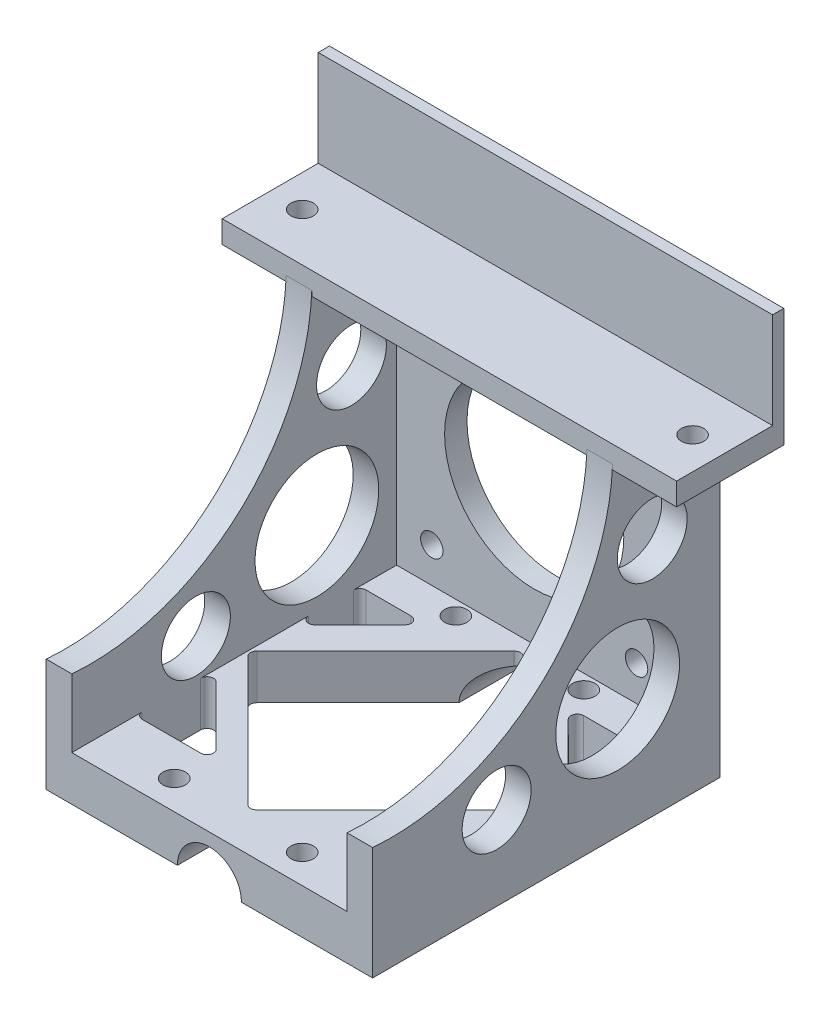
SolidWorks part; units mm, degrees
ref_plane "Front Plane" through (0, 0, 0) normal (0, 0, 1) x (1, 0, 0)
ref_plane "Top Plane" through (0, 0, 0) normal (0, 1, 0) x (1, 0, 0)
ref_plane "Right Plane" through (0, 0, 0) normal (1, 0, 0) x (0, 0, -1)
sketch "Sketch1" plane through (0, 0, 0) normal (0, 0, 1) x (1, 0, 0)
  line L1 (-51.9324, 28.7717) -> (-0.9324, 28.7717)
  line L2 (-51.9324, 28.7717) -> (-51.9324, -24.7283)
  line L3 (-51.9324, -24.7283) -> (-0.9324, -24.7283)
  line L4 (-0.9324, 28.7717) -> (-0.9324, -24.7283)
  dimension "D1" = 51
  dimension "D2" = 53.5
extrude "Boss-Extrude1" add sketch "Sketch1" along normal blind 54.25
sketch "Sketch2" plane through (0, 0, 54.25) normal (0, 0, 1) x (1, 0, 0)
  line L0 (-0.9324, -24.7283) -> (-0.9324, 28.7717) construction
  line L1 (-47.9324, -17.7283) -> (-4.9324, -17.7283)
  line L2 (-47.9324, -17.7283) -> (-47.9324, 25.2717)
  line L3 (-47.9324, 25.2717) -> (-4.9324, 25.2717)
  line L4 (-4.9324, -17.7283) -> (-4.9324, 25.2717)
  line L6 (-51.9324, -24.7283) -> (-0.9324, -24.7283) construction
  dimension "D1" = 43
  dimension "D2" = 43
  dimension "D3" = 4
  dimension "D4" = 7
extrude "Cut-Extrude1" cut sketch "Sketch2" against normal offset from surface (50.75 mm away) 3.5 up to face at (-26.4324, 2.0217, 0)
sketch "Sketch3" plane through (0, 0, 54.25) normal (0, 0, 1) x (1, 0, 0)
  line L0 (-0.9324, 28.7717) -> (-51.9324, 28.7717) construction
  line L1 (-47.9324, 25.2717) -> (-4.9324, 25.2717)
  line L2 (-47.9324, 25.2717) -> (-47.9324, 28.7717)
  line L3 (-47.9324, 28.7717) -> (-4.9324, 28.7717)
  line L4 (-4.9324, 25.2717) -> (-4.9324, 28.7717)
extrude "Cut-Extrude2" cut sketch "Sketch3" against normal offset from surface (37.5 mm away) 16.75 up to face at (-26.4324, 2.0217, 0)
sketch "Sketch4" plane through (-51.9324, 0, 0) normal (-1, 0, 0) x (0, 0, 1)
  line L0 (16.75, 25.2717) -> (16.75, 28.7717) construction
  line L1 (54.25, 28.7717) -> (54.25, -24.7283) construction
  line L3 (16.75, 28.7717) -> (54.25, 28.7717)
  line L4 (54.25, 28.7717) -> (54.25, -7.0747)
  arc A0 (16.75, 28.7717) -> (54.25, -7.0747) centre (51.3457, 27.4252) ccw
extrude "Cut-Extrude3" cut sketch "Sketch4" against normal blind 76
sketch "Sketch5" plane through (-51.9324, 0, 0) normal (-1, 0, 0) x (0, 0, 1)
  circle A0 centre (15.9549, -6.117) radius 9.6731
  circle A1 centre (34.8683, -11.6526) radius 5.3908
  circle A2 centre (10.5511, 12.8623) radius 5.4569
extrude "Cut-Extrude4" cut sketch "Sketch5" against normal blind 76
sketch "Sketch6" plane through (0, 0, 3.5) normal (0, 0, 1) x (1, 0, 0)
  line L0 (-4.9324, 25.2717) -> (-47.9324, -17.7283) construction
  line L1 (-4.9324, -17.7283) -> (-47.9324, 25.2717) construction
  circle A0 centre (-26.4324, 3.7717) radius 14
  circle A1 centre (-10.4324, 19.7717) radius 1.75
  circle A2 centre (-42.4324, 19.7717) radius 1.75
  circle A3 centre (-42.4324, -12.2283) radius 1.75
  circle A4 centre (-10.4324, -12.2283) radius 1.75
  dimension "D2" = 28
  dimension "D3" = 3.5
  dimension "D1" = 32
extrude "Cut-Extrude5" cut sketch "Sketch6" against normal blind 76
sketch "Sketch7" plane through (0, 0, 0) normal (0, 0, -1) x (-1, 0, 0)
  line L0 (51.9324, -24.7283) -> (0.9324, -24.7283) construction
  circle A0 centre (26.4324, -24.7283) radius 5
  dimension "D1" = 10
extrude "Cut-Extrude6" cut sketch "Sketch7" against normal blind 76
sketch "Sketch8" plane through (0, -24.7283, 0) normal (0, -1, 0) x (1, 0, 0)
  line L0 (-26.4324, 54.25) -> (-26.4324, 0) construction
  line L1 (-21.4324, 54.25) -> (-31.4324, 54.25) construction
  line L2 (-31.4324, 0) -> (-21.4324, 0) construction
  line L3 (-26.4324, 48.25) -> (-4.9324, 26.75)
  line L4 (-4.9324, 3.5) -> (-4.9324, 54.25) construction
  line L5 (-4.9324, 26.75) -> (-26.4324, 5.25)
  line L7 (-26.4324, 5.25) -> (-47.9324, 26.75)
  line L8 (-47.9324, 26.75) -> (-26.4324, 48.25)
  line L9 (-47.9324, 3.5) -> (-47.9324, 54.25) construction
  line L10 (-26.4324, 5.25) -> (-4.9324, 5.25) construction
  line L11 (-26.4324, 5.25) -> (-47.9324, 5.25) construction
  line L12 (-26.4324, 48.25) -> (-47.9324, 48.25) construction
  line L13 (-26.4324, 48.25) -> (-4.9324, 48.25) construction
  line L14 (-15.3613, 44.25) -> (-4.9324, 44.25)
  line L15 (-4.9324, 44.25) -> (-4.9324, 33.8211)
  line L16 (-4.9324, 33.8211) -> (-15.3613, 44.25)
  line L17 (-4.9324, 9.25) -> (-15.3613, 9.25)
  line L18 (-15.3613, 9.25) -> (-4.9324, 19.6789)
  line L19 (-4.9324, 19.6789) -> (-4.9324, 9.25)
  line L20 (-47.9324, 9.25) -> (-37.5034, 9.25)
  line L21 (-37.5034, 9.25) -> (-47.9324, 19.6789)
  line L22 (-47.9324, 19.6789) -> (-47.9324, 9.25)
  line L23 (-47.9324, 44.25) -> (-35.3821, 44.25)
  line L24 (-35.3821, 44.25) -> (-47.9324, 31.6997)
  line L25 (-47.9324, 31.6997) -> (-47.9324, 44.25)
  dimension "D1" = 6
  dimension "D2" = 45
  dimension "D3" = 4
  dimension "D4" = 45
  dimension "D5" = 5
  dimension "D6" = 4
  dimension "D7" = 5
  dimension "D8" = 5
extrude "Cut-Extrude7" cut sketch "Sketch8" against normal blind 27
fillet "Fillet2" radius 1 16 edges at (-47.9324, -21.2283, 31.6997) (-4.9324, -21.2283, 33.8211) (-4.9324, -21.2283, 19.6789) (-47.9324, -21.2283, 19.6789) (-15.3613, -21.2283, 9.25) (-37.5034, -21.2283, 9.25) (-26.4324, -18.7283, 5.25) (-4.9324, -21.2283, 9.25) (-47.9324, -21.2283, 9.25) (-47.9324, -21.2283, 26.75) (-4.9324, -21.2283, 26.75) (-4.9324, -21.2283, 44.25) (-47.9324, -21.2283, 44.25) (-35.3821, -21.2283, 44.25) (-15.3613, -21.2283, 44.25) (-26.4324, -18.7283, 48.25)
sketch "Sketch12" plane through (0, -24.7283, 0) normal (0, -1, 0) x (1, 0, 0)
  line L0 (-21.4324, 54.25) -> (-0.9324, 54.25) construction
  line L1 (-47.9324, 54.25) -> (-4.9324, 54.25) construction
  line L2 (-21.4324, 54.25) -> (-31.4324, 54.25) construction
  line L3 (-21.4324, 0) -> (-0.9324, 0) construction
  circle A0 centre (-16.4324, 49.75) radius 1.75
  circle A1 centre (-36.4324, 49.75) radius 1.75
  circle A2 centre (-16.4324, 5.75) radius 1.75
  circle A3 centre (-36.4324, 5.75) radius 1.75
  point P10 (-26.4324, 54.25)
  point P13 (-26.4324, 54.25)
  dimension "D1" = 4.5
  dimension "D2" = 10
  dimension "D3" = 10
  dimension "D4" = 5.75
extrude "Cut-Extrude8" cut sketch "Sketch12" against normal blind 15
sketch "Sketch13" plane through (-51.9324, 0, 0) normal (-1, 0, 0) x (0, 0, 1)
  line L0 (3.5, 25.2717) -> (16.75, 25.2717) construction
  line L1 (0, 28.7717) -> (16.75, 28.7717)
  line L2 (0, 28.7717) -> (0, 25.2717)
  line L3 (0, 25.2717) -> (16.75, 25.2717)
  line L4 (16.75, 28.7717) -> (16.75, 25.2717)
  line L5 (16.75, 28.7717) -> (0, 28.7717) construction
  arc A0 (16.75, 28.7717) -> (54.25, -7.0747) centre (51.3457, 27.4252) ccw construction
extrude "Boss-Extrude4" add sketch "Sketch13" along normal blind 10 and the other way offset from surface (61 mm away) 10 other way up to face at (-0.9324, 7.4054, 10.5511)
sketch "Sketch14" plane through (0, 28.7717, 0) normal (0, 1, 0) x (1, 0, 0)
  line L0 (9.0676, 0) -> (9.0676, -16.75) construction
  line L1 (-61.9324, 0) -> (9.0676, 0)
  line L2 (-61.9324, 0) -> (-61.9324, -1.75)
  line L3 (-61.9324, -1.75) -> (9.0676, -1.75)
  line L4 (9.0676, 0) -> (9.0676, -1.75)
  dimension "D1" = 1.75
extrude "Boss-Extrude5" add sketch "Sketch14" along normal blind 15
sketch "Sketch15" plane through (0, 25.2717, 0) normal (0, -1, 0) x (1, 0, 0)
  line L0 (4.0676, 0) -> (4.0676, 16.75) construction
  line L1 (9.0676, 0) -> (-0.9324, 0) construction
  line L2 (9.0676, 16.75) -> (-0.9324, 16.75) construction
  line L3 (9.0676, 9.25) -> (-61.9324, 9.25) construction
  line L6 (-56.9324, 16.75) -> (-56.9324, 0) construction
  line L7 (-51.9324, 16.75) -> (-61.9324, 16.75) construction
  line L8 (-51.9324, 0) -> (-61.9324, 0) construction
  circle A0 centre (-56.9324, 9.25) radius 1.75
  circle A1 centre (4.0676, 9.25) radius 1.75
  dimension "D1" = 3.5
  dimension "D2" = 7.5
extrude "Cut-Extrude9" cut sketch "Sketch15" against normal blind 10
